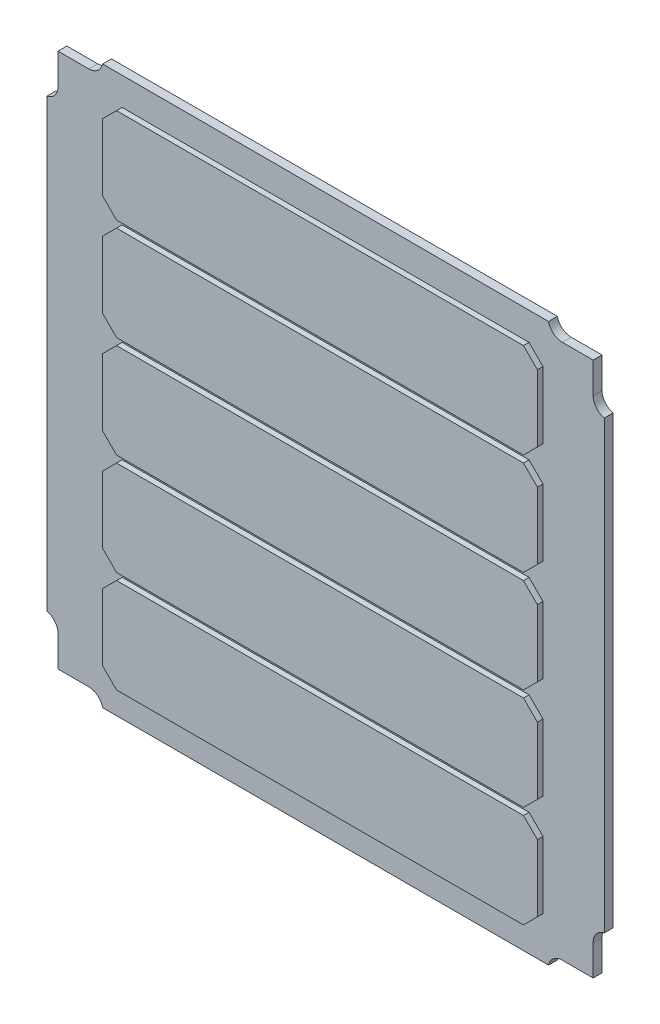
SolidWorks part; units mm, degrees
ref_plane "Front Plane" through (0, 0, 0) normal (0, 0, 1) x (1, 0, 0)
ref_plane "Top Plane" through (0, 0, 0) normal (0, 1, 0) x (1, 0, 0)
ref_plane "Right Plane" through (0, 0, 0) normal (1, 0, 0) x (0, 0, -1)
sketch "Sketch1" plane through (0, 0, 0) normal (0, 0, 1) x (1, 0, 0)
  line L0 (-40, 50) -> (-40, 48)
  line L1 (-50, -50) -> (50, -50)
  line L2 (-50, -50) -> (-50, 50)
  line L3 (-50, 50) -> (50, 50)
  line L4 (50, -50) -> (50, 50)
  line L5 (-50, -50) -> (50, 50) construction
  line L6 (-50, 50) -> (50, -50) construction
  line L7 (-50, 50) -> (-40, 50)
  line L8 (-50, 50) -> (-50, 40)
  line L9 (-40, 48) -> (-48, 48)
  line L10 (-48, 48) -> (-48, 40)
  line L11 (50, 50) -> (40, 50)
  line L12 (50, 50) -> (50, 40)
  line L13 (-48, 40) -> (-50, 40)
  line L14 (50, 40) -> (48, 40)
  line L15 (-50, -50) -> (-37.8649, -50)
  line L16 (-50, -50) -> (-50, -37.8649)
  line L17 (50, 50) -> (50, 40)
  line L18 (50, 50) -> (40, 50)
  line L19 (50, -50) -> (41.5, -50)
  line L20 (50, -50) -> (50, -41.5)
  line L21 (48, 40) -> (48, 48)
  line L22 (48, 48) -> (40, 48)
  line L23 (40, 48) -> (40, 50)
  line L24 (40, -50) -> (40, -48)
  line L25 (50, -50) -> (40, -50)
  line L26 (50, -50) -> (50, -40)
  line L27 (40, -48) -> (48, -48)
  line L28 (48, -48) -> (48, -40)
  line L29 (48, -40) -> (50, -40)
  line L30 (-50, -40) -> (-48, -40)
  line L31 (-50, -50) -> (-50, -40)
  line L32 (-50, -50) -> (-40, -50)
  line L33 (-48, -40) -> (-48, -48)
  line L34 (-48, -48) -> (-40, -48)
  line L35 (-40, -48) -> (-40, -50)
  point P0 (0, 0)
  point P38 (0, 0)
  dimension "D1" = 100
  dimension "D2" = 100
  dimension "D3" = 2
  dimension "D4" = 10
  dimension "D5" = 4
extrude "Boss-Extrude1" add sketch "Sketch1" along normal blind 1.5875 contours L1 L4 L3 L2 region at (0, 0, 0)
sketch "Sketch2" plane through (0, 0, 1.5875) normal (0, 0, 1) x (1, 0, 0)
  line L0 (-36.5, 45) -> (36.5, 45)
  line L1 (-39, 42.5) -> (-36.5, 45)
  line L2 (39, 42.5) -> (39, 30.5)
  line L3 (36.5, 28) -> (-36.5, 28)
  line L4 (-39, 30.5) -> (-39, 42.5)
  line L5 (-36.5, 28) -> (-39, 30.5)
  line L6 (0, 0) -> (0, 50) construction
  line L7 (36.5, 45) -> (39, 42.5)
  line L8 (39, 30.5) -> (36.5, 28)
  line L9 (-36.5, 26.75) -> (36.5, 26.75)
  line L10 (-39, 24.25) -> (-36.5, 26.75)
  line L11 (39, 24.25) -> (39, 12.25)
  line L12 (36.5, 9.75) -> (-36.5, 9.75)
  line L13 (-39, 12.25) -> (-39, 24.25)
  line L14 (-36.5, 9.75) -> (-39, 12.25)
  line L15 (36.5, 26.75) -> (39, 24.25)
  line L16 (39, 12.25) -> (36.5, 9.75)
  line L17 (-36.5, 8.5) -> (36.5, 8.5)
  line L18 (-39, 6) -> (-36.5, 8.5)
  line L19 (39, 6) -> (39, -6)
  line L20 (36.5, -8.5) -> (-36.5, -8.5)
  line L21 (-39, -6) -> (-39, 6)
  line L22 (-36.5, -8.5) -> (-39, -6)
  line L23 (36.5, 8.5) -> (39, 6)
  line L24 (39, -6) -> (36.5, -8.5)
  line L25 (-36.5, -9.75) -> (36.5, -9.75)
  line L26 (-39, -12.25) -> (-36.5, -9.75)
  line L27 (39, -12.25) -> (39, -24.25)
  line L28 (36.5, -26.75) -> (-36.5, -26.75)
  line L29 (-39, -24.25) -> (-39, -12.25)
  line L30 (-40, 50) -> (40, 50) construction
  line L33 (-36.5, -26.75) -> (-39, -24.25)
  line L34 (36.5, -9.75) -> (39, -12.25)
  line L36 (39, -24.25) -> (36.5, -26.75)
  line L37 (-36.5, -28) -> (36.5, -28)
  line L38 (-39, -30.5) -> (-36.5, -28)
  line L39 (39, -30.5) -> (39, -42.5)
  line L40 (36.5, -45) -> (-36.5, -45)
  line L41 (-39, -42.5) -> (-39, -30.5)
  line L42 (-36.5, -45) -> (-39, -42.5)
  line L43 (36.5, -28) -> (39, -30.5)
  line L44 (39, -42.5) -> (36.5, -45)
  line L45 (-40, -50) -> (40, -50) construction
  point P0 (-39, 45)
  point P3 (39, 45)
  point P4 (39, 28)
  point P5 (-39, 28)
  point P19 (-39, 26.75)
  point P21 (39, 26.75)
  point P22 (39, 9.75)
  point P23 (-39, 9.75)
  point P31 (-39, 8.5)
  point P33 (39, 8.5)
  point P34 (39, -8.5)
  point P35 (-39, -8.5)
  point P43 (-39, -9.75)
  point P45 (39, -9.75)
  point P46 (39, -26.75)
  point P47 (-39, -26.75)
  point P55 (-39, -28)
  point P57 (39, -28)
  point P58 (39, -45)
  point P59 (-39, -45)
  dimension "D1" = 78
  dimension "D2" = 17
  dimension "D3" = 5
  dimension "D4" = 5
  dimension "D5" = 5
extrude "Boss-Extrude2" add sketch "Sketch2" along normal blind 1
fillet "Fillet1" radius 2.54 8 edges at (-48, -40, 0.7937) (-40, -48, 0.7937) (40, -48, 0.7937) (48, -40, 0.7937) (48, 40, 0.7937) (40, 48, 0.7937) (-40, 48, 0.7937) (-48, 40, 0.7937)
